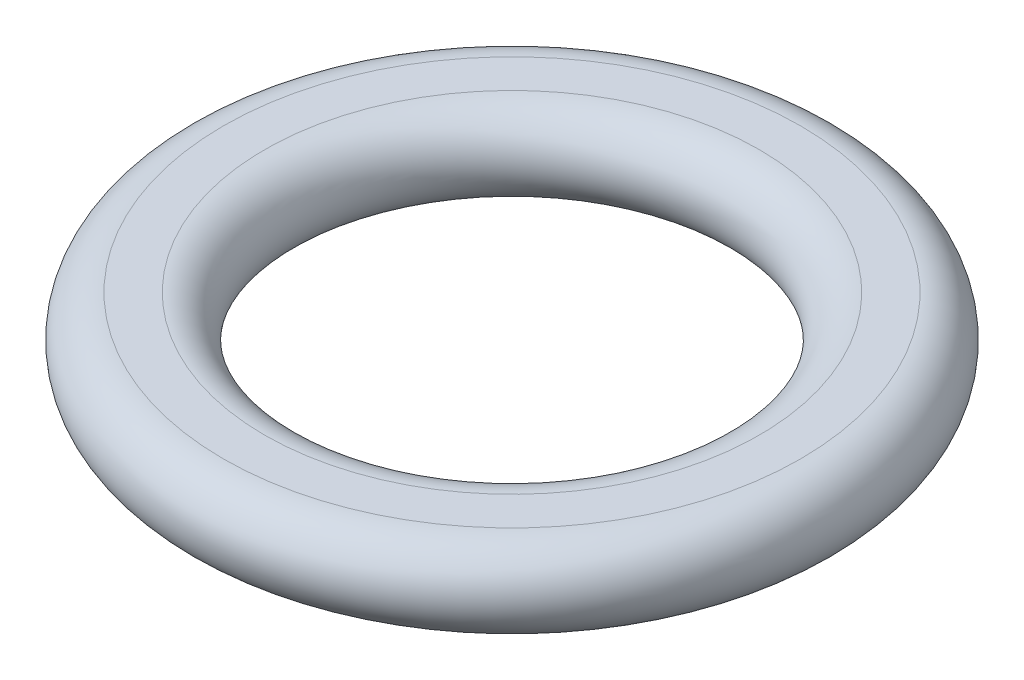
SolidWorks part; units mm, degrees
material "Silicon Rubber"
ref_plane "Front Plane" through (0, 0, 0) normal (0, 0, 1) x (1, 0, 0)
ref_plane "Top Plane" through (0, 0, 0) normal (0, 1, 0) x (1, 0, 0)
ref_plane "Right Plane" through (0, 0, 0) normal (1, 0, 0) x (0, 0, -1)
ref_axis "CentralAxis" through (0, 0.715, 0) along (0, -1, 0)
sketch "ProfileS" plane through (0, 0, 0) normal (0, 0, 1) x (1, 0, 0)
  line L0 (3, 0) -> (3.5, 0) construction
  line L1 (3, 0.5) -> (3.5, 0.5)
  line L2 (3, -0.5) -> (3.5, -0.5)
  line L3 (0, 0.5) -> (0, -0.5) construction
  arc A0 (3, 0.5) -> (3, -0.5) centre (3, 0) ccw
  arc A1 (3.5, -0.5) -> (3.5, 0.5) centre (3.5, 0) ccw
  point P2 (3.25, 0)
  point P8 (2.5, 0)
  point P9 (4, 0)
  dimension "Height" = 1
  dimension "ID" = 5
  dimension "OD" = 8
revolve "Profile" add sketch "ProfileS" angle 360 about L3
